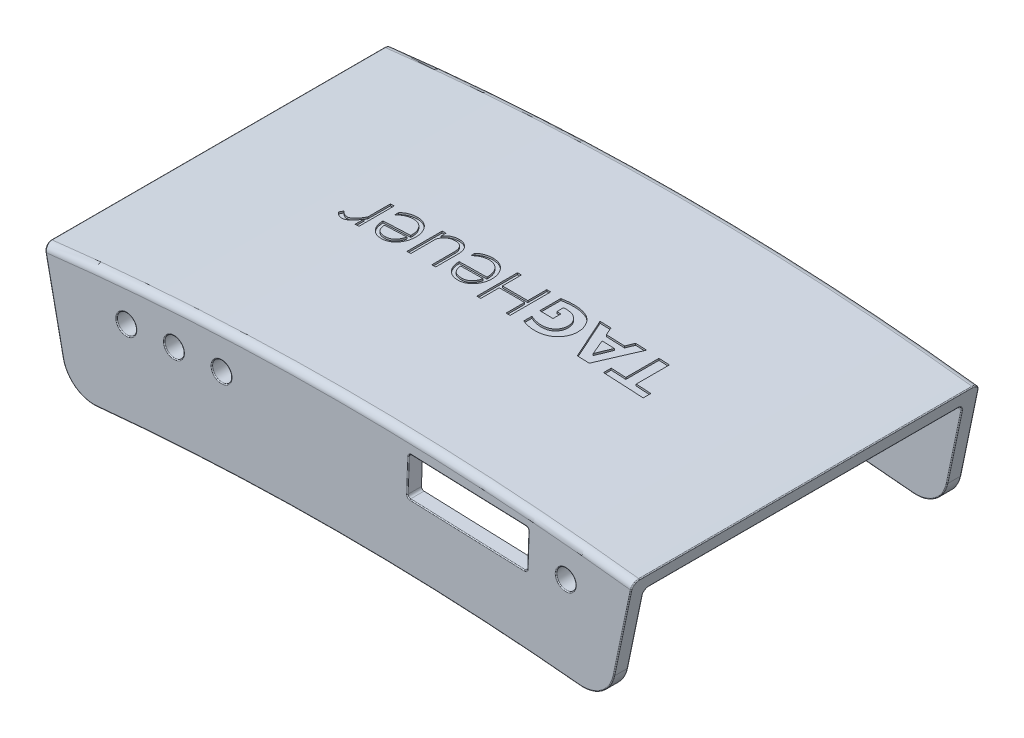
SolidWorks part; units mm, degrees
ref_plane "Front Plane" through (0, 0, 0) normal (0, 0, 1) x (1, 0, 0)
ref_plane "Top Plane" through (0, 0, 0) normal (0, 1, 0) x (1, 0, 0)
ref_plane "Right Plane" through (0, 0, 0) normal (1, 0, 0) x (0, 0, -1)
sketch "Sketch1" plane through (0, 0, 0) normal (0, 0, 1) x (1, 0, 0)
  line L0 (0, -55) -> (0, 55) construction
  line L1 (-16.9, 3.85) -> (16.9, 3.85)
  line L2 (-16.9, 3.85) -> (-16.9, -3.85)
  line L3 (-16.9, -3.85) -> (16.9, -3.85)
  line L4 (16.9, 3.85) -> (16.9, -3.85)
  line L5 (55, 0) -> (-55, 0) construction
  dimension "D1" = 33.8
  dimension "D2" = 16.9
  dimension "D3" = 7.7
  dimension "D4" = 3.85
extrude "Boss-Extrude1" add sketch "Sketch1" along normal mid plane 19.7
sketch "Sketch2" plane through (0, 0, 9.85) normal (0, 0, 1) x (1, 0, 0)
  line L0 (-16.9, 3.85) -> (-15.3, -3.85)
  line L1 (-16.9, -3.85) -> (16.9, -3.85) construction
  line L2 (-15.3, -3.85) -> (-22.2111, -8.6776)
  line L3 (-22.2111, -8.6776) -> (-16.9, 3.85)
  line L4 (16.9, 3.85) -> (15.3, -3.85)
  line L5 (15.3, -3.85) -> (23.1776, -10.33)
  line L6 (23.1776, -10.33) -> (16.9, 3.85)
  line L7 (-16.9, 3.85) -> (-16.9, -3.85) construction
  line L8 (16.9, -3.85) -> (16.9, 3.85) construction
  dimension "D1" = 1.6
  dimension "D2" = 1.6
extrude "Cut-Extrude1" cut sketch "Sketch2" against normal blind 29.7
sketch "Sketch3" plane through (0, 0, 9.85) normal (0, 0, 1) x (1, 0, 0)
  line L0 (10.835, 0) -> (-10.835, 0) construction
  line L1 (0, -7.799) -> (0, 7.799) construction
  line L2 (-15.3, -3.85) -> (-15.3, -6.0261)
  line L3 (-15.3, -6.0261) -> (15.3, -6.0261)
  line L4 (15.3, -6.0261) -> (15.3, -3.85)
  line L5 (17, 2.8) -> (18.6757, 6.2707)
  line L6 (18.6757, 6.2707) -> (-0.269, 12.5728)
  line L7 (-0.269, 12.5728) -> (-23.7866, 9.4217)
  line L8 (-23.7866, 9.4217) -> (-17, 2.8)
  arc A0 (-15.3, -3.85) -> (15.3, -3.85) centre (0, -143.0115) cw
  arc A1 (-17, 2.8) -> (17, 2.8) centre (0, -136.164) cw
  dimension "D1" = 140
  dimension "D6" = 140
  dimension "D2" = 2.8
  dimension "D3" = 2.8
  dimension "D4" = 17
  dimension "D5" = 17
extrude "Cut-Extrude2" cut sketch "Sketch3" against normal blind 29.7
fillet "Fillet1" radius 1.8 2 edges at (15.3, -3.85, 0) (-15.3, -3.85, 0)
sketch "Sketch7" plane through (0, 0, 9.85) normal (0, 0, 1) x (1, 0, 0)
  arc A0 (16.386, 0.759) -> (-16.386, 0.759) centre (0, -136.164) ccw
sketch "Sketch4" plane through (0, 0, 9.85) normal (0, 0, 1) x (1, 0, 0)
  line L0 (3.989, 2.8568) -> (10.789, 2.6089)
  line L1 (10.789, 2.6089) -> (10.7088, 0.4089)
  line L2 (10.7088, 0.4089) -> (3.9088, 0.6568)
  line L3 (3.9088, 0.6568) -> (3.989, 2.8568)
  circle A0 centre (12.9007, 1.1312) radius 0.55
  circle A1 centre (-12.029, 1.2103) radius 0.55
  circle A2 centre (-9.329, 1.4201) radius 0.55
  circle A3 centre (-6.629, 1.5766) radius 0.55
  arc A5 (16.386, 0.759) -> (-16.386, 0.759) centre (0, -136.164) ccw construction
  dimension "D1" = 1.1
  dimension "D2" = 1.1
  dimension "D3" = 1.1
  dimension "D4" = 1.1
  dimension "D7" = 2.7
  dimension "D8" = 2.7
  dimension "D5" = 2.2
  dimension "D6" = 6.8
extrude "Cut-Extrude3" cut sketch "Sketch4" against normal blind 29.7
sketch "Sketch5" plane through (0, 0, 0) normal (0, 0, 1) x (1, 0, 0)
  line L0 (-16.5943, 2.0433) -> (-24.1736, -2.3754)
  line L1 (-24.1736, -2.3754) -> (-13.1304, -14.0637)
  line L2 (-13.1304, -14.0637) -> (25.6536, -10.0031)
  line L3 (25.6536, -10.0031) -> (16.5943, 2.0433)
  arc A2 (16.5943, 2.0433) -> (-16.5943, 2.0433) centre (0, -136.164) ccw
  arc A3 (16.5943, 2.0433) -> (-16.5943, 2.0433) centre (0, -136.164) ccw
  dimension "D1" = 0.8
extrude "Cut-Extrude4" cut sketch "Sketch5" against normal mid plane 18.1
fillet "Fillet2" radius 0.4 2 edges at (0, 3.836, -9.85) (0, 3.836, 9.85)
fillet "Fillet3" radius 0.3 2 edges at (0, 3.036, 9.05) (0, 3.036, -9.05)
fillet "Fillet4" radius 0.05 32 edges at (-16.5129, 1.9873, 8.9369) (-16.5263, 2.0515, 0) (-16.5034, 1.9413, -8.9838) (-16.048, -0.2504, -9.05) (-14.9348, -3.3415, -9.05) (0, -3.0115, -9.05) (14.9348, -3.3415, -9.05) (16.048, -0.2504, -9.05) (16.5129, 1.9873, -8.9369) (16.5263, 2.0515, 0) (16.5034, 1.9413, 8.9838) (16.048, -0.2504, 9.05) (14.9348, -3.3415, 9.05) (0, -3.0115, 9.05) (-14.9348, -3.3415, 9.05) (-14.9348, -3.3415, 9.85) (0, -3.0115, 9.85) (14.9348, -3.3415, 9.85) (16.1194, 0.0935, 9.85) (16.6718, 2.752, 9.6992) (16.6896, 2.8376, 0) (16.6591, 2.6908, -9.7618) (16.1194, 0.0935, -9.85) (14.9348, -3.3415, -9.85) (0, -3.0115, -9.85) (-14.9348, -3.3415, -9.85) (-16.1194, 0.0935, -9.85) (-16.6718, 2.752, -9.6992) (-16.6896, 2.8376, 0) (-16.6591, 2.6908, 9.7618) (-16.048, -0.2504, 9.05) (-16.1194, 0.0935, 9.85)
fillet "Fillet5" radius 0.15 8 edges at (10.7088, 0.4089, 9.45) (3.9088, 0.6568, 9.45) (10.789, 2.6089, 9.335) (3.989, 2.8568, 9.4207) (3.9088, 0.6568, -9.45) (10.7088, 0.4089, -9.45) (10.789, 2.6089, -9.335) (3.989, 2.8568, -9.4207)
fillet "Fillet6" radius 0.05 24 edges at (10.6665, 0.4544, 9.85) (7.3088, 0.5329, 9.85) (3.9543, 0.6991, 9.85) (3.9489, 1.7568, 9.85) (4.0313, 2.8113, 9.85) (7.389, 2.7329, 9.85) (10.7435, 2.5666, 9.85) (10.6665, 0.4544, -9.85) (7.3088, 0.5329, -9.85) (3.9543, 0.6991, -9.85) (3.9489, 1.7568, -9.85) (4.0313, 2.8113, -9.85) (7.389, 2.7329, -9.85) (10.7435, 2.5666, -9.85) (10.7489, 1.5089, 9.85) (13.4507, 1.1312, 9.85) (-6.079, 1.5766, 9.85) (-8.779, 1.4201, 9.85) (-11.479, 1.2103, 9.85) (-11.479, 1.2103, -9.85) (-8.779, 1.4201, -9.85) (-6.079, 1.5766, -9.85) (10.7489, 1.5089, -9.85) (13.4507, 1.1312, -9.85)
sketch "Sketch6" plane through (0, 0, 0) normal (0, 1, 0) x (1, 0, 0)
  line L0 (7.1975, 1.1415) -> (7.1975, -0.7385)
  line L1 (7.1975, -0.7385) -> (6.3674, -0.7385)
  line L2 (6.3674, -0.7385) -> (6.3674, -1.1755)
  line L3 (6.3674, -1.1755) -> (8.6169, -1.1755)
  line L4 (8.6169, -1.1755) -> (8.6169, -0.7385)
  line L5 (8.6169, -0.7385) -> (7.7867, -0.7385)
  line L6 (7.7867, -0.7385) -> (7.7867, 1.1415)
  line L7 (7.7867, 1.1415) -> (7.1975, 1.1415)
  line L8 (1.7034, -1.0321) -> (1.7034, -0.5743)
  line L9 (2.1734, 0.7455) -> (2.1734, 0.3725)
  line L10 (2.1734, 0.3725) -> (2.4021, 0.3732)
  line L11 (2.4021, 0.3732) -> (2.4021, -0.0764)
  line L12 (2.4021, -0.0764) -> (1.6522, -0.0764)
  line L13 (1.6522, -0.0764) -> (1.6522, 1.1177)
  line L14 (1.6522, 1.1177) -> (1.6517, 1.1177)
  line L15 (-0.6142, 0.0703) -> (-0.6135, 1.1482)
  line L16 (-0.6135, 1.1482) -> (-0.8369, 1.1482)
  line L17 (-0.8369, 1.1482) -> (-0.8369, -1.1579)
  line L18 (-0.8369, -1.1579) -> (-0.6135, -1.1579)
  line L19 (-0.6135, -1.1579) -> (-0.6142, -0.1088)
  line L20 (-0.6142, -0.1088) -> (0.8241, -0.1088)
  line L21 (0.8241, -0.1088) -> (0.8236, -1.1579)
  line L22 (0.8236, -1.1579) -> (1.047, -1.1579)
  line L23 (1.047, -1.1579) -> (1.047, 1.1482)
  line L24 (1.047, 1.1482) -> (0.8236, 1.1482)
  line L25 (0.8236, 1.1482) -> (0.8241, 0.0703)
  line L26 (0.8241, 0.0703) -> (-0.6142, 0.0703)
  line L27 (-3.7035, 0.445) -> (-3.7035, -0.849)
  line L28 (-3.7035, -0.849) -> (-3.481, -0.849)
  line L29 (-3.481, -0.849) -> (-3.4807, 0.3974)
  line L30 (-4.8893, 0.8476) -> (-4.8886, 1.1467)
  line L31 (-4.8886, 1.1467) -> (-5.112, 1.1467)
  line L32 (-5.112, 1.1467) -> (-5.112, -0.849)
  line L33 (-5.112, -0.849) -> (-4.8893, -0.849)
  line L34 (-4.8893, -0.849) -> (-4.8886, 0.5723)
  line L35 (-8.0538, -0.3495) -> (-8.0545, -0.8461)
  line L36 (-8.0545, -0.8461) -> (-7.8311, -0.8461)
  line L37 (-7.8311, -0.8461) -> (-7.8311, 1.1497)
  line L38 (-7.8311, 1.1497) -> (-8.0538, 1.1497)
  line L39 (-8.0538, 1.1497) -> (-8.0545, -0.1189)
  line L40 (-9.0837, -0.4463) -> (-9.2031, -0.6513)
  line L41 (5.6829, 0.7016) -> (5.8608, 1.1555)
  line L42 (5.8608, 1.1555) -> (6.4819, 1.1555)
  line L43 (6.4819, 1.1555) -> (5.5362, -1.1556)
  line L44 (5.5362, -1.1556) -> (4.8626, -1.1556)
  line L45 (4.8626, -1.1556) -> (3.8394, 1.1555)
  line L46 (3.8394, 1.1555) -> (4.4604, 1.1555)
  line L47 (4.4604, 1.1555) -> (4.6501, 0.7016)
  line L48 (4.6501, 0.7016) -> (5.6829, 0.7016)
  line L49 (4.8287, 0.2817) -> (5.1882, -0.5823)
  line L50 (5.1882, -0.5823) -> (5.5205, 0.2817)
  line L51 (5.5205, 0.2817) -> (4.8287, 0.2817)
  line L52 (-3.0303, 0.6943) -> (-3.0303, 0.9252)
  line L53 (-3.068, 0.072) -> (-1.4988, 0.072)
  line L54 (-1.5267, -0.1103) -> (-2.8054, -0.1103)
  line L55 (-7.3498, 0.6943) -> (-7.3498, 0.9252)
  line L56 (-7.3878, 0.072) -> (-5.8186, 0.072)
  line L57 (-5.8465, -0.1103) -> (-7.1249, -0.1103)
  spline S0 degree 3 poles (1.6517, 1.1177) (2.1036, 1.2193) (2.6848, 1.2491) (3.1048, 1.056) knots 0 0 0 0 1 1 1 1
  spline S1 degree 3 poles (3.1048, 1.056) (3.4631, 0.8988) (3.6841, 0.5244) (3.7299, 0.1581) knots 1 1 1 1 2 2 2 2
  spline S2 degree 3 poles (3.7299, 0.1581) (3.7776, -0.2917) (3.6084, -0.6859) (3.2481, -0.9506) knots 2 2 2 2 3 3 3 3
  spline S3 degree 3 poles (3.2481, -0.9506) (2.8281, -1.2511) (2.1613, -1.2412) (1.7034, -1.0321) knots 3 3 3 3 4 4 4 4
  spline S4 degree 3 poles (1.7034, -0.5743) (2.0498, -0.7335) (2.5713, -0.8271) (2.9037, -0.5743) knots 7 7 7 7 8 8 8 8
  spline S5 degree 3 poles (2.9037, -0.5743) (3.1426, -0.3912) (3.2163, -0.1006) (3.1566, 0.19) knots 8 8 8 8 9 9 9 9
  spline S6 degree 3 poles (3.1566, 0.19) (3.1088, 0.419) (2.9117, 0.626) (2.6928, 0.7016) knots 9 9 9 9 10 10 10 10
  spline S7 degree 3 poles (2.6928, 0.7016) (2.5375, 0.7514) (2.3466, 0.7674) (2.1734, 0.7455) knots 10 10 10 10 11 11 11 11
  spline S8 degree 2 poles (-4.8886, 0.5723) (-4.7353, 1.015) (-4.2376, 1.015) knots 0 0 0 1 1 1
  spline S9 degree 3 poles (-4.2376, 1.015) (-3.8328, 1.015) (-3.7035, 0.7311) (-3.7035, 0.445) knots 1 1 1 1 2 2 2 2
  spline S10 degree 3 poles (-3.4807, 0.3974) (-3.4807, 1.1521) (-4.046, 1.1942) (-4.2027, 1.1942) knots 7 7 7 7 8 8 8 8
  spline S11 degree 2 poles (-4.2027, 1.1942) (-4.678, 1.1942) (-4.8893, 0.8476) knots 8 8 8 9 9 9
  spline S12 degree 2 poles (-9.2031, -0.6513) (-8.9994, -0.8812) (-8.7445, -0.8812) knots 0 0 0 1 1 1
  spline S13 degree 2 poles (-8.7445, -0.8812) (-8.4032, -0.8812) (-8.0538, -0.3495) knots 1 1 1 2 2 2
  spline S14 degree 2 poles (-8.0545, -0.1189) (-8.3708, -0.668) (-8.6731, -0.668) knots 9 9 9 10 10 10
  spline S15 degree 2 poles (-8.6731, -0.668) (-8.8805, -0.668) (-9.0837, -0.4463) knots 10 10 10 11 11 11
  spline S16 degree 3 poles (-1.4988, 0.072) (-1.4975, 0.0951) (-1.4968, 0.117) (-1.4968, 0.1405) knots 0 0 0 0 1 1 1 1
  spline S17 degree 3 poles (-1.4968, 0.1405) (-1.4968, 0.6283) (-1.8173, 0.9927) (-2.2917, 0.9927) knots 1 1 1 1 2 2 2 2
  spline S18 degree 2 poles (-2.2917, 0.9927) (-2.7198, 0.9927) (-3.0303, 0.6943) knots 2 2 2 3 3 3
  spline S19 degree 2 poles (-3.0303, 0.9252) (-2.7421, 1.1905) (-2.2668, 1.1905) knots 6 6 6 7 7 7
  spline S20 degree 3 poles (-2.2668, 1.1905) (-1.5452, 1.1905) (-1.2603, 0.576) (-1.2603, 0.1429) knots 7 7 7 7 8 8 8 8
  spline S21 degree 3 poles (-1.2603, 0.1429) (-1.2603, -0.4227) (-1.6277, -0.8892) (-2.1619, -0.8892) knots 8 8 8 8 9 9 9 9
  spline S22 degree 3 poles (-2.1619, -0.8892) (-2.7657, -0.8892) (-3.068, -0.4206) (-3.068, 0.072) knots 9 9 9 9 10 10 10 10
  spline S23 degree 2 poles (-2.8054, -0.1103) (-2.7633, -0.6857) (-2.1607, -0.6857) knots 2 2 2 3 3 3
  spline S24 degree 3 poles (-2.1607, -0.6857) (-1.8205, -0.6857) (-1.601, -0.4329) (-1.5267, -0.1103) knots 3 3 3 3 4 4 4 4
  spline S25 degree 3 poles (-5.8186, 0.072) (-5.8171, 0.0951) (-5.8163, 0.117) (-5.8163, 0.1405) knots 0 0 0 0 1 1 1 1
  spline S26 degree 3 poles (-5.8163, 0.1405) (-5.8163, 0.6283) (-6.1369, 0.9927) (-6.6114, 0.9927) knots 1 1 1 1 2 2 2 2
  spline S27 degree 2 poles (-6.6114, 0.9927) (-7.0393, 0.9927) (-7.3498, 0.6943) knots 2 2 2 3 3 3
  spline S28 degree 2 poles (-7.3498, 0.9252) (-7.0618, 1.1905) (-6.5865, 1.1905) knots 6 6 6 7 7 7
  spline S29 degree 3 poles (-6.5865, 1.1905) (-5.8649, 1.1905) (-5.5799, 0.576) (-5.5799, 0.1429) knots 7 7 7 7 8 8 8 8
  spline S30 degree 3 poles (-5.5799, 0.1429) (-5.5799, -0.4227) (-5.9475, -0.8892) (-6.4816, -0.8892) knots 8 8 8 8 9 9 9 9
  spline S31 degree 3 poles (-6.4816, -0.8892) (-7.0855, -0.8892) (-7.3878, -0.4206) (-7.3878, 0.072) knots 9 9 9 9 10 10 10 10
  spline S32 degree 2 poles (-7.1249, -0.1103) (-7.083, -0.6857) (-6.4803, -0.6857) knots 2 2 2 3 3 3
  spline S33 degree 3 poles (-6.4803, -0.6857) (-6.1402, -0.6857) (-5.9207, -0.4329) (-5.8465, -0.1103) knots 3 3 3 3 4 4 4 4
extrude "Cut-Extrude5" cut sketch "Sketch6" against normal offset from surface (6.2738 mm away) 0.1 from offset 10
